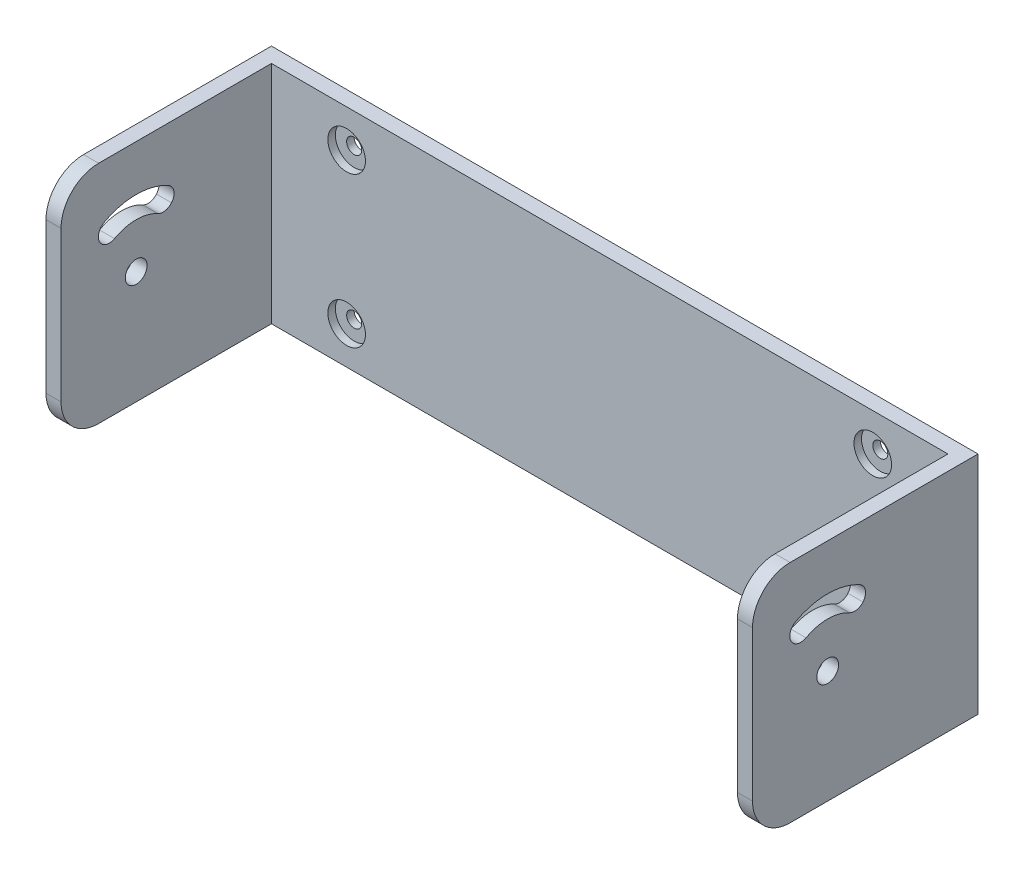
SolidWorks part; units mm, degrees
ref_plane "前视基准面" through (0, 0, 0) normal (0, 0, 1) x (1, 0, 0)
ref_plane "上视基准面" through (0, 0, 0) normal (0, 1, 0) x (1, 0, 0)
ref_plane "右视基准面" through (0, 0, 0) normal (1, 0, 0) x (0, 0, -1)
other "Configuration Table"
sketch "草图1" plane through (0, 0, 0) normal (0, 0, 1) x (1, 0, 0)
  line L1 (-90, 30) -> (90, 30)
  line L2 (-90, 30) -> (-90, -30)
  line L3 (-90, -30) -> (90, -30)
  line L4 (90, 30) -> (90, -30)
  dimension "D1" = 60
  dimension "D2" = 180
  dimension "D3" = 90
  dimension "D4" = 30
extrude "凸台-拉伸1" add sketch "草图1" along normal blind 4
sketch "草图4" plane through (0, 0, 4) normal (0, 0, 1) x (1, 0, 0)
  line L1 (-70, 20) -> (70, 20) construction
  line L2 (-70, 20) -> (-70, -20) construction
  line L3 (-70, -20) -> (70, -20) construction
  line L4 (70, 20) -> (70, -20) construction
  circle A0 centre (-70, 20) radius 2
  circle A1 centre (-70, -20) radius 2
  circle A2 centre (70, 20) radius 2
  circle A3 centre (70, -20) radius 2
  dimension "D5" = 4
  dimension "D6" = 4
  dimension "D7" = 4
  dimension "D8" = 4
  dimension "D1" = 40
  dimension "D2" = 140
  dimension "D3" = 70
  dimension "D4" = 20
extrude "切除-拉伸2" cut sketch "草图4" against normal blind 50
sketch "草图8" plane through (0, 0, 4) normal (0, 0, 1) x (1, 0, 0)
  circle A1 centre (70, 20) radius 5
  circle A2 centre (-70, 20) radius 5
  circle A3 centre (-70, -20) radius 5
  circle A4 centre (70, -20) radius 5
  dimension "D1" = 10
  dimension "D2" = 10
  dimension "D3" = 10
  dimension "D4" = 10
extrude "切除-拉伸6" cut sketch "草图8" against normal blind 2
sketch "草图9" plane through (90, 0, 0) normal (1, 0, 0) x (0, 0, -1)
  line L0 (-4, 30) -> (0, 30) construction
  line L1 (0, -30) -> (-60, -30)
  line L2 (0, -30) -> (0, 30)
  line L3 (0, 30) -> (-60, 30)
  line L4 (-60, -30) -> (-60, 30)
  dimension "D1" = 60
extrude "凸台-拉伸2" add sketch "草图9" along normal blind 4
sketch "草图10" plane through (-90, 0, 0) normal (-1, 0, 0) x (0, 0, 1)
  line L1 (0, 30) -> (60, 30)
  line L2 (0, 30) -> (0, -30)
  line L3 (0, -30) -> (60, -30)
  line L4 (60, 30) -> (60, -30)
extrude "凸台-拉伸3" add sketch "草图10" along normal blind 4
sketch "草图11" plane through (-94, 0, 0) normal (-1, 0, 0) x (0, 0, 1)
  line L0 (60, -30) -> (60, 30) construction
  line L1 (0, -30) -> (60, -30) construction
  line L4 (40, 2.9) -> (40, 17.8) construction
  line L5 (47.7135, 9.1925) -> (51.4416, 13.6356)
  line L6 (32.2865, 9.1925) -> (28.5584, 13.6356)
  circle A0 centre (40, 0) radius 2.9
  arc A1 (47.7135, 9.1925) -> (32.2865, 9.1925) centre (40, 0) ccw
  arc A2 (51.4416, 13.6356) -> (28.5584, 13.6356) centre (40, 0) ccw
  dimension "D1" = 5.8
  dimension "D4" = 24
  dimension "D5" = 35.6
  dimension "D2" = 20
  dimension "D3" = 30
  dimension "D6" = 40
  dimension "D7" = 40
  dimension "D8" = 5.8
  dimension "D9" = 5.8
extrude "切除-拉伸7" cut sketch "草图11" against normal through all both and the other way through all
fillet "圆角1" radius 2.9 4 edges at (-92, 13.6356, 51.4416) (-92, 9.1925, 47.7135) (-92, 13.6356, 28.5584) (-92, 9.1925, 32.2865)
fillet "圆角2" radius 2.9 4 edges at (92, 13.6356, 28.5584) (92, 13.6356, 51.4416) (92, 9.1925, 47.7135) (92, 9.1925, 32.2865)
fillet "圆角3" radius 10 4 edges at (-92, 30, 60) (-92, -30, 60) (92, -30, 60) (92, 30, 60)
